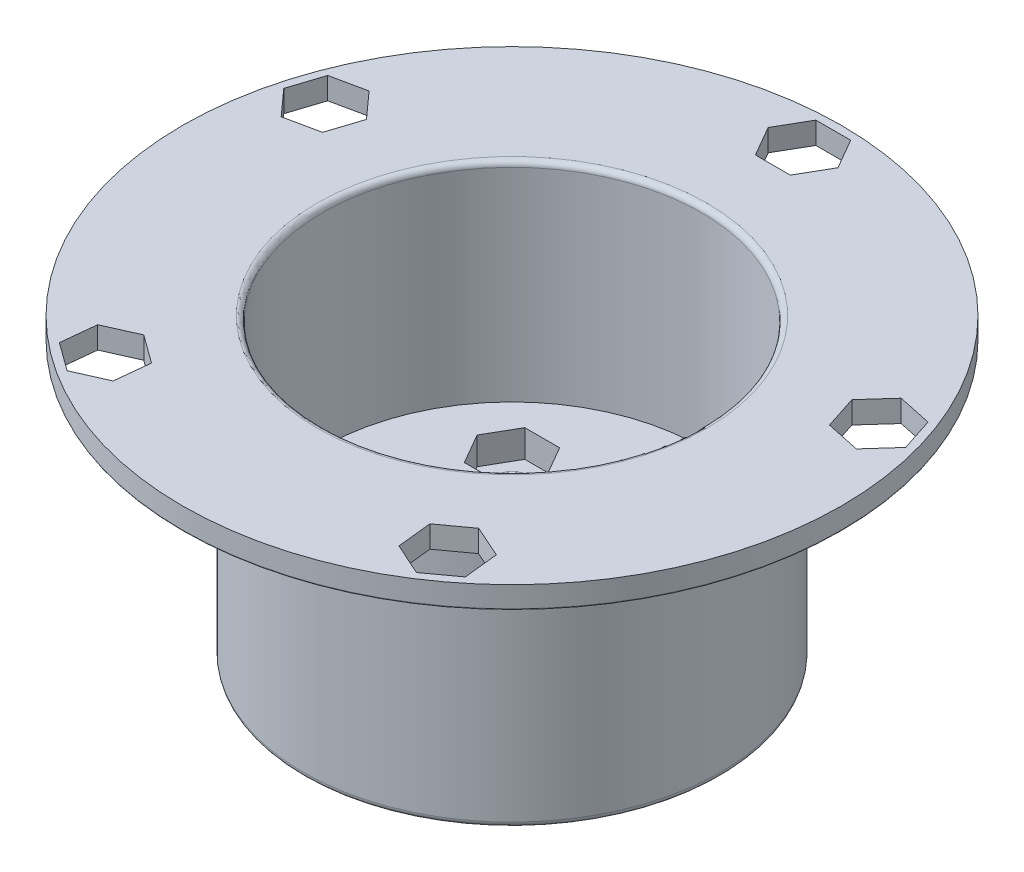
SolidWorks part; units mm, degrees
ref_plane "前视基准面" through (0, 0, 0) normal (0, 0, 1) x (1, 0, 0)
ref_plane "上视基准面" through (0, 0, 0) normal (0, 1, 0) x (1, 0, 0)
ref_plane "右视基准面" through (0, 0, 0) normal (1, 0, 0) x (0, 0, -1)
other "Configuration Table"
sketch "草图1" plane through (0, 0, 0) normal (0, 1, 0) x (1, 0, 0)
  circle A1 centre (0, 0) radius 19
  circle A2 centre (0, 0) radius 8 construction
  circle A3 centre (0, 8) radius 1.25
  circle A4 centre (8, 0) radius 1.25
  circle A5 centre (0, -8) radius 1.25
  circle A6 centre (-8, 0) radius 1.25
  point P15 (0, 0)
  dimension "D1" = 16
  dimension "D2" = 38
  dimension "D3" = 2.5
  dimension "D4" = 4
extrude "凸台-拉伸1" add sketch "草图1" along normal blind 8
sketch "草图2" plane through (0, 8, 0) normal (0, 1, 0) x (1, 0, 0)
  circle A0 centre (0, 0) radius 17
  circle A1 centre (0, 0) radius 19
  circle A2 centre (0, 0) radius 19
  dimension "D2" = 34
  dimension "D1" = 0
extrude "凸台-拉伸2" add sketch "草图2" along normal blind 19
sketch "草图3" plane through (0, 27, 0) normal (0, 1, 0) x (1, 0, 0)
  circle A0 centre (0, 0) radius 30
  circle A1 centre (0, 0) radius 19
  circle A2 centre (0, 0) radius 19
  dimension "D2" = 60
  dimension "D1" = 0
extrude "凸台-拉伸3" add sketch "草图3" against normal blind 2 separate body
combine bodies "组合1" operation type add bodies to combine 108 107
sketch "草图4" plane through (0, 8, 0) normal (0, 1, 0) x (1, 0, 0)
  circle A0 centre (0, 0) radius 5.2
  dimension "D1" = 10.4
extrude "切除-拉伸1" cut sketch "草图4" against normal up to next
sketch "草图5" plane through (0, 0, 0) normal (0, -1, 0) x (1, 0, 0)
  circle A0 centre (0, 8) radius 2.1
  circle A1 centre (8, 0) radius 2.1
  circle A2 centre (0, -8) radius 2.1
  circle A3 centre (-8, 0) radius 2.1
  point P12 (0, 0)
  dimension "D1" = 4.2
  dimension "D2" = 4
extrude "切除-拉伸2" cut sketch "草图5" against normal blind 6.2
sketch "草图6" plane through (0, 0, 0) normal (0, -1, 0) x (1, 0, 0)
  line L5 (-8, 8) -> (8, 8) construction
  line L7 (-8, 8) -> (-8, -8) construction
  line L8 (-8, -8) -> (8, -8) construction
  line L9 (8, 8) -> (8, -8) construction
  line L10 (-8, 8) -> (8, -8) construction
  line L11 (-8, -8) -> (8, 8) construction
  circle A1 centre (-8, 8) radius 1.6
  circle A2 centre (8, 8) radius 1.6
  circle A3 centre (8, -8) radius 1.6
  circle A4 centre (-8, -8) radius 1.6
  point P0 (0, 0)
  point P17 (0, 0)
  dimension "D4" = 3.2
  dimension "D1" = 16
  dimension "D2" = 16
  dimension "D3" = 4
extrude "切除-拉伸3" cut sketch "草图6" against normal up to next
sketch "草图7" plane through (0, 8, 0) normal (0, 1, 0) x (1, 0, 0)
  line L0 (-5.2, 0) -> (0, 0) construction
  line L1 (-6.4123, 10.75) -> (-9.5877, 10.75)
  line L2 (-9.5877, 10.75) -> (-11.1754, 8)
  line L3 (-11.1754, 8) -> (-9.5877, 5.25)
  line L4 (-9.5877, 5.25) -> (-6.4123, 5.25)
  line L5 (-6.4123, 5.25) -> (-4.8246, 8)
  line L6 (-4.8246, 8) -> (-6.4123, 10.75)
  line L7 (0, 0) -> (0, 5.2) construction
  line L8 (4.8246, 8) -> (6.4123, 10.75)
  line L9 (6.4123, 5.25) -> (4.8246, 8)
  line L10 (9.5877, 5.25) -> (6.4123, 5.25)
  line L11 (11.1754, 8) -> (9.5877, 5.25)
  line L12 (9.5877, 10.75) -> (11.1754, 8)
  line L13 (6.4123, 10.75) -> (9.5877, 10.75)
  line L14 (-4.8246, -8) -> (-6.4123, -10.75)
  line L15 (-6.4123, -5.25) -> (-4.8246, -8)
  line L16 (-9.5877, -5.25) -> (-6.4123, -5.25)
  line L17 (-11.1754, -8) -> (-9.5877, -5.25)
  line L18 (-9.5877, -10.75) -> (-11.1754, -8)
  line L19 (-6.4123, -10.75) -> (-9.5877, -10.75)
  line L20 (6.4123, -5.25) -> (4.8246, -8)
  line L21 (9.5877, -5.25) -> (6.4123, -5.25)
  line L22 (11.1754, -8) -> (9.5877, -5.25)
  line L23 (9.5877, -10.75) -> (11.1754, -8)
  line L24 (6.4123, -10.75) -> (9.5877, -10.75)
  line L25 (4.8246, -8) -> (6.4123, -10.75)
  circle A0 centre (-8, 8) radius 2.75 construction
  circle A1 centre (0, 0) radius 5.2 construction
  dimension "D1" = 5.5
extrude "切除-拉伸4" cut sketch "草图7" against normal blind 2.5
sketch "草图9" plane through (0, 0, 0) normal (0, -1, 0) x (1, 0, 0)
  line L1 (-11.5, 11.5) -> (11.5, 11.5)
  line L2 (-11.5, 11.5) -> (-11.5, -11.5)
  line L3 (-11.5, -11.5) -> (11.5, -11.5)
  line L4 (11.5, 11.5) -> (11.5, -11.5)
  line L5 (-11.5, 11.5) -> (11.5, -11.5) construction
  line L6 (-11.5, -11.5) -> (11.5, 11.5) construction
  point P0 (0, 0)
  dimension "D1" = 23
  dimension "D2" = 23
extrude "切除-拉伸5" cut sketch "草图9" against normal blind 1.6
fillet "圆角1" radius 4 4 edges at (11.5, 0.8, 11.5) (-11.5, 0.8, 11.5) (-11.5, 0.8, -11.5) (11.5, 0.8, -11.5)
sketch "草图10" plane through (0, 1.6, 0) normal (0, -1, 0) x (1, 0, 0)
  line L8 (10.5, -7.5) -> (10.5, 7.5)
  line L9 (7.5, 10.5) -> (-7.5, 10.5)
  line L10 (-10.5, 7.5) -> (-10.5, -7.5)
  line L11 (-7.5, -10.5) -> (7.5, -10.5)
  line L12 (10.5, -7.5) -> (10.5, 7.5)
  line L13 (7.5, 10.5) -> (-7.5, 10.5)
  line L14 (-10.5, 7.5) -> (-10.5, -7.5)
  line L15 (-7.5, -10.5) -> (7.5, -10.5)
  arc A8 (10.5, 7.5) -> (7.5, 10.5) centre (7.5, 7.5) ccw
  arc A9 (-7.5, 10.5) -> (-10.5, 7.5) centre (-7.5, 7.5) ccw
  arc A10 (-10.5, -7.5) -> (-7.5, -10.5) centre (-7.5, -7.5) ccw
  arc A11 (7.5, -10.5) -> (10.5, -7.5) centre (7.5, -7.5) ccw
  arc A12 (10.5, 7.5) -> (7.5, 10.5) centre (7.5, 7.5) ccw
  arc A13 (-7.5, 10.5) -> (-10.5, 7.5) centre (-7.5, 7.5) ccw
  arc A14 (-10.5, -7.5) -> (-7.5, -10.5) centre (-7.5, -7.5) ccw
  arc A15 (7.5, -10.5) -> (10.5, -7.5) centre (7.5, -7.5) ccw
  dimension "D1" = 1
extrude "切除-拉伸6" cut sketch "草图10" against normal blind 1.6
sketch "草图11" plane through (0, 27, 0) normal (0, 1, 0) x (1, 0, 0)
  circle A0 centre (0, 0) radius 17.25
  dimension "D1" = 34.5
extrude "切除-拉伸7" cut sketch "草图11" against normal up to surface (19 mm away) up to face at (8, 8, -8)
sketch "草图12" plane through (0, 27, 0) normal (0, 1, 0) x (1, 0, 0)
  circle A0 centre (0, 0) radius 26.5 construction
  circle A1 centre (0, 26.5) radius 1.5
  circle A2 centre (25.203, 8.189) radius 1.5
  circle A3 centre (15.5763, -21.439) radius 1.5
  circle A4 centre (-15.5763, -21.439) radius 1.5
  circle A5 centre (-25.203, 8.189) radius 1.5
  point P15 (0, 0)
  dimension "D1" = 53
  dimension "D2" = 3
  dimension "D3" = 5
extrude "切除-拉伸8" cut sketch "草图12" against normal up to next
sketch "草图14" plane through (0, 25, 0) normal (0, -1, 0) x (1, 0, 0)
  line L0 (-22.097, -8.8492) -> (-23.0782, -5.8291)
  line L1 (1.5877, -23.75) -> (-1.5877, -23.75)
  line L2 (-1.5877, -23.75) -> (-3.1754, -26.5)
  line L3 (-3.1754, -26.5) -> (-1.5877, -29.25)
  line L4 (-1.5877, -29.25) -> (1.5877, -29.25)
  line L5 (1.5877, -29.25) -> (3.1754, -26.5)
  line L6 (3.1754, -26.5) -> (1.5877, -23.75)
  line L7 (-23.0782, -5.8291) -> (-26.1843, -5.1689)
  line L8 (-26.1843, -5.1689) -> (-28.309, -7.5287)
  line L9 (-28.309, -7.5287) -> (-27.3278, -10.5488)
  line L10 (-27.3278, -10.5488) -> (-24.2217, -11.209)
  line L11 (-24.2217, -11.209) -> (-22.097, -8.8492)
  line L12 (-15.2444, 18.2809) -> (-12.6754, 20.1474)
  line L13 (-12.6754, 20.1474) -> (-13.0073, 23.3054)
  line L14 (-13.0073, 23.3054) -> (-15.9082, 24.597)
  line L15 (-15.9082, 24.597) -> (-18.4772, 22.7305)
  line L16 (-18.4772, 22.7305) -> (-18.1453, 19.5725)
  line L17 (-18.1453, 19.5725) -> (-15.2444, 18.2809)
  line L18 (12.6754, 20.1474) -> (15.2444, 18.2809)
  line L19 (15.2444, 18.2809) -> (18.1453, 19.5725)
  line L20 (18.1453, 19.5725) -> (18.4772, 22.7305)
  line L21 (18.4772, 22.7305) -> (15.9082, 24.597)
  line L22 (15.9082, 24.597) -> (13.0073, 23.3054)
  line L23 (13.0073, 23.3054) -> (12.6754, 20.1474)
  line L24 (23.0782, -5.8291) -> (22.097, -8.8492)
  line L25 (22.097, -8.8492) -> (24.2217, -11.209)
  line L26 (24.2217, -11.209) -> (27.3278, -10.5488)
  line L27 (27.3278, -10.5488) -> (28.309, -7.5287)
  line L28 (28.309, -7.5287) -> (26.1843, -5.1689)
  line L29 (26.1843, -5.1689) -> (23.0782, -5.8291)
  circle A0 centre (0, -26.5) radius 2.75 construction
  point P35 (0, 0)
  dimension "D1" = 5.5
  dimension "D2" = 5
extrude "切除-拉伸9" cut sketch "草图14" against normal blind 2
fillet "圆角2" radius 0.5 1 edges at (0, 27, 17.25)
fillet "圆角3" radius 0.5 1 edges at (0, 0, 19)
fillet "圆角4" radius 0.25 2 edges at (0, 3.2, -5.2) (0, 8, 5.2)
fillet "圆角5" radius 0.1 19 edges at (8, 3.2, -9.6) (8, 5.5, -9.6) (0, 6.2, -9.25) (0, 8, -6.75) (-8, 3.2, -9.6) (-8, 5.5, -6.4) (-8, 6.2, -1.25) (-8, 8, 1.25) (-8, 3.2, 6.4) (-8, 5.5, 6.4) (0, 6.2, 6.75) (0, 8, 9.25) (8, 3.2, 6.4) (8, 5.5, 9.6) (8, 6.2, -1.25) (8, 8, 1.25) (-8, 3.2, -2.1) (0, 3.2, 5.9) (0, 3.2, -10.1)
fillet "圆角6" radius 0.1 1 edges at (0, 25, 30)
